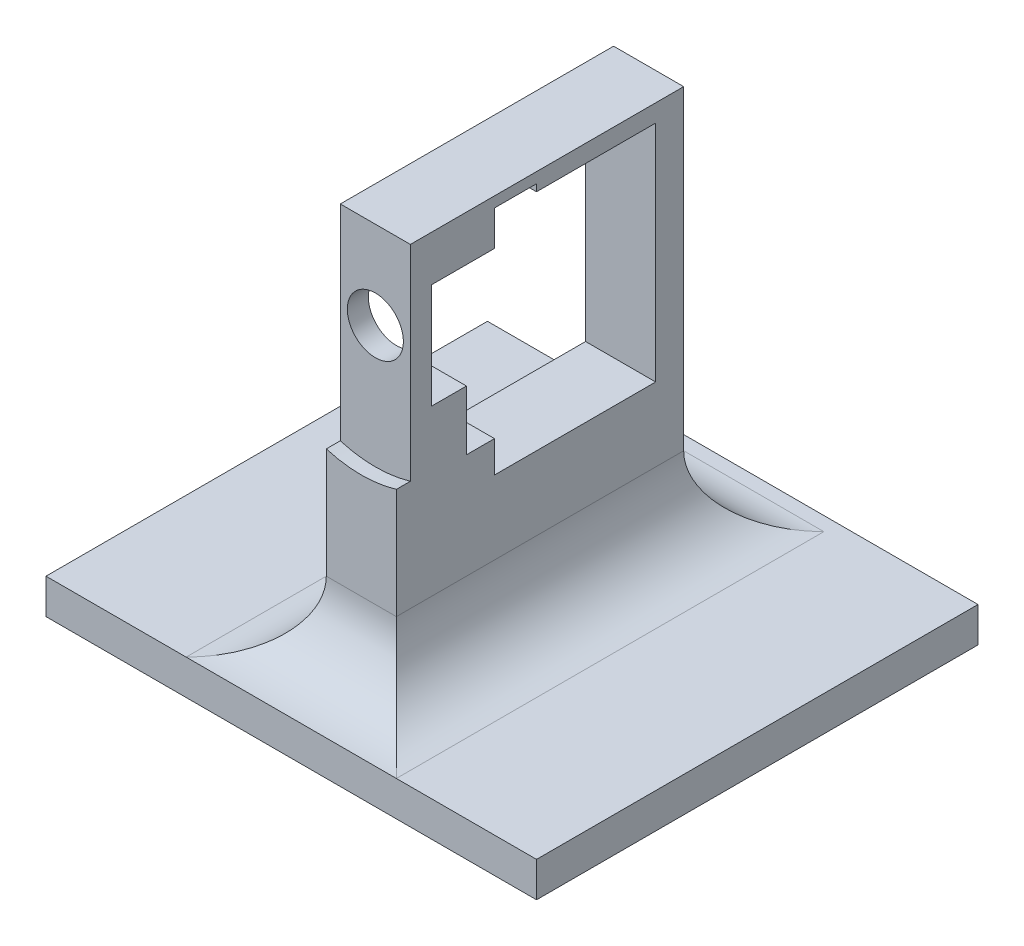
SolidWorks part; units mm, degrees
ref_plane "Front Plane" through (0, 0, 0) normal (0, 0, 1) x (1, 0, 0)
ref_plane "Top Plane" through (0, 0, 0) normal (0, 1, 0) x (1, 0, 0)
ref_plane "Right Plane" through (0, 0, 0) normal (1, 0, 0) x (0, 0, -1)
sketch "Sketch1" plane through (0, 0, 0) normal (0, 0, 1) x (1, 0, 0)
  line L1 (-35, 2.5) -> (35, 2.5)
  line L2 (-35, 2.5) -> (-35, -2.5)
  line L3 (-35, -2.5) -> (35, -2.5)
  line L4 (35, 2.5) -> (35, -2.5)
  line L5 (-35, 2.5) -> (35, -2.5) construction
  line L6 (-35, -2.5) -> (35, 2.5) construction
  point P0 (0, 0)
  dimension "D1" = 5
  dimension "D2" = 70
extrude "Boss-Extrude1" add sketch "Sketch1" along normal blind 20 and the other way blind 43
sketch "Sketch2" plane through (0, 0, 0) normal (0, 0, 1) x (1, 0, 0)
  line L0 (35, 2.5) -> (-35, 2.5) construction
  line L1 (5, 2.5) -> (-5, 2.5)
  line L2 (5, 2.5) -> (5, 57.5)
  line L3 (5, 57.5) -> (-5, 57.5)
  line L4 (-5, 2.5) -> (-5, 57.5)
  point P6 (0, 2.5)
  dimension "D1" = 0
  dimension "D2" = 10
  dimension "D3" = 55
extrude "Boss-Extrude2" add sketch "Sketch2" along normal blind 10 and the other way blind 10
sketch "Sketch4" plane through (0, 0, 10) normal (0, 0, 1) x (1, 0, 0)
  circle A0 centre (0, 45) radius 17.5
  circle A1 centre (0, 45) radius 1.25
  line M3 (-5, 57.5) -> (-5, 2.5)
  line M5 (5, 2.5) -> (5, 57.5)
  line M6 (5, 57.5) -> (-5, 57.5)
  dimension "D2" = 35
  dimension "D3" = 2.5
  dimension "D1" = 45
  dimension "D4" = 0
extrude "Cut-Extrude2" cut sketch "Sketch4" against normal blind 2 and the other way blind 10 contours A0 M5 M3 M6 | A0 A1 M3 M5 M6 region at (13.6385, 34.8345, 10) region at (0, 42.5798, 10)
sketch "Sketch5" plane through (0, 0, 10) normal (0, 0, 1) x (1, 0, 0)
  circle A0 centre (0, 45) radius 1.25
extrude "Cut-Extrude3" cut sketch "Sketch5" against normal up to surface (20 mm away) up to face at (0, 30, -10)
sketch "Sketch6" plane through (-5, 0, 0) normal (-1, 0, 0) x (0, 0, 1)
  line L0 (-7.1132, 45) -> (14.6472, 45) construction
  line L1 (8, 28.2295) -> (8, 57.5) construction
  line L2 (0, 51) -> (5, 51)
  line L3 (-10, 23) -> (-10, 27.5)
  line L4 (-10, 57.5) -> (-10, 2.5) construction
  line L5 (0, 51) -> (0, 36)
  line L6 (-23, 51) -> (0, 51)
  line L7 (-23, 51) -> (-23, 27.5)
  line L8 (-23, 27.5) -> (0, 27.5)
  line L9 (0, 51) -> (0, 27.5)
  line L10 (-7, 56) -> (-4, 56)
  line L11 (-7, 56) -> (-7, 23)
  line L12 (-7, 23) -> (-4, 23)
  line L13 (-4, 56) -> (-4, 23)
  line L14 (0, 36) -> (5, 36)
  line L15 (5, 51) -> (5, 36)
  line L16 (-10, 56) -> (-7, 56)
  line L17 (-7, 23) -> (-23, 23)
  line L18 (-7, 23) -> (-7, 56)
  line L19 (-7, 56) -> (-23, 56)
  line L20 (-23, 23) -> (-23, 56)
  line M6 (-10, 57.5) -> (-10, 2.5)
  dimension "D1" = 45
  dimension "D2" = 15
  dimension "D3" = 5
  dimension "D4" = 23.5
  dimension "D5" = 6
  dimension "D6" = 23
  dimension "D7" = 3
  dimension "D8" = 4
  dimension "D9" = 33
  dimension "D10" = 22
  dimension "D11" = 3
extrude "Cut-Extrude4" cut sketch "Sketch6" against normal up to surface (10 mm away) contours L13 L8 L11 L12 | L17 L11 L8 M6 | L0 L8 L18 M6 | L0 L11 L6 M6 | L16 L6 L11 M6 | L13 L10 L11 L6 | L11 L0 L13 L6 | L13 L0 L5 L6 | L5 L0 L15 L2 | L0 L9 L14 L15 | L0 L13 L8 L9 | L0 L18 L8 L13 region at (-5, 48, -5.5) region at (-5, 39.25, -8.5) region at (-5, 36.25, -5.5) region at (-5, 48, -2) region at (-5, 36.25, -2) region at (-5, 53.5, -5.5) region at (-5, 53.5, -8.5) region at (-5, 25.25, -8.5) region at (-5, 25.25, -5.5) region at (-5, 48, 2.5) region at (-5, 40.5, 2.5) up to face at (5, 29.4098, 2.6667)
sketch "Sketch7" plane through (0, 0, 5) normal (0, 0, -1) x (-1, 0, 0)
  circle A0 centre (0, 45) radius 4
  dimension "D1" = 8
extrude "Cut-Extrude5" cut sketch "Sketch7" against normal blind 6
sketch "Sketch8" plane through (-5, 0, 0) normal (-1, 0, 0) x (0, 0, 1)
  line L1 (-10, 57.5) -> (-31, 57.5)
  line L2 (-10, 57.5) -> (-10, 55)
  line L3 (-10, 55) -> (-31, 55)
  line L4 (-31, 57.5) -> (-31, 55)
  line L5 (8, 45) -> (-46.6892, 45) construction
  line L6 (-31, 55) -> (-27, 55)
  line L7 (-31, 55) -> (-31, 40)
  line L8 (-31, 40) -> (-27, 40)
  line L9 (-27, 55) -> (-27, 40)
  line L10 (8, 28.2295) -> (8, 57.5) construction
  line L12 (-10, 57.5) -> (8, 57.5) construction
  line L13 (-43, 2.5) -> (20, 2.5) construction
  line L14 (-31, 40) -> (-27, 40)
  line L15 (-31, 40) -> (-31, 2.5)
  line L16 (-31, 2.5) -> (-27, 2.5)
  line L17 (-27, 40) -> (-27, 2.5)
  line L19 (-10, 23) -> (-27, 23)
  line L20 (-10, 23) -> (-10, 2.5)
  line L21 (-10, 2.5) -> (-27, 2.5)
  line L22 (-27, 23) -> (-27, 2.5)
  line M10 (-10, 57.5) -> (-10, 56)
  line M20 (-10, 23) -> (-10, 2.5)
  dimension "D1" = 35
  dimension "D2" = 12.5
  dimension "D3" = 5
  dimension "D4" = 4
extrude "Boss-Extrude3" add sketch "Sketch8" against normal up to surface (10 mm away) contours L5 L9 L3 L7 | L1 L4 L3 M10 | L9 L5 L7 L8 | L17 L8 L15 L16 | L21 L20 L19 L17 M20 region at (-5, 56.25, -20.5) region at (-5, 50, -29) region at (-5, 42.5, -29) region at (-5, 21.25, -29) region at (-5, 12.75, -18.5) up to face at (5, 35.2162, -0.625)
sketch "Sketch9" plane through (0, 0, -27) normal (0, 0, 1) x (1, 0, 0)
  circle A0 centre (0, 45) radius 2
  dimension "D1" = 4
extrude "Boss-Extrude4" add sketch "Sketch9" against normal blind 8
fillet "Fillet2" radius 2 1 edges at (2, 45, -35)
fillet "Fillet1" radius 10 4 edges at (-5, 2.5, -10.5) (0, 2.5, 10) (5, 2.5, -10.5) (0, 2.5, -31)
